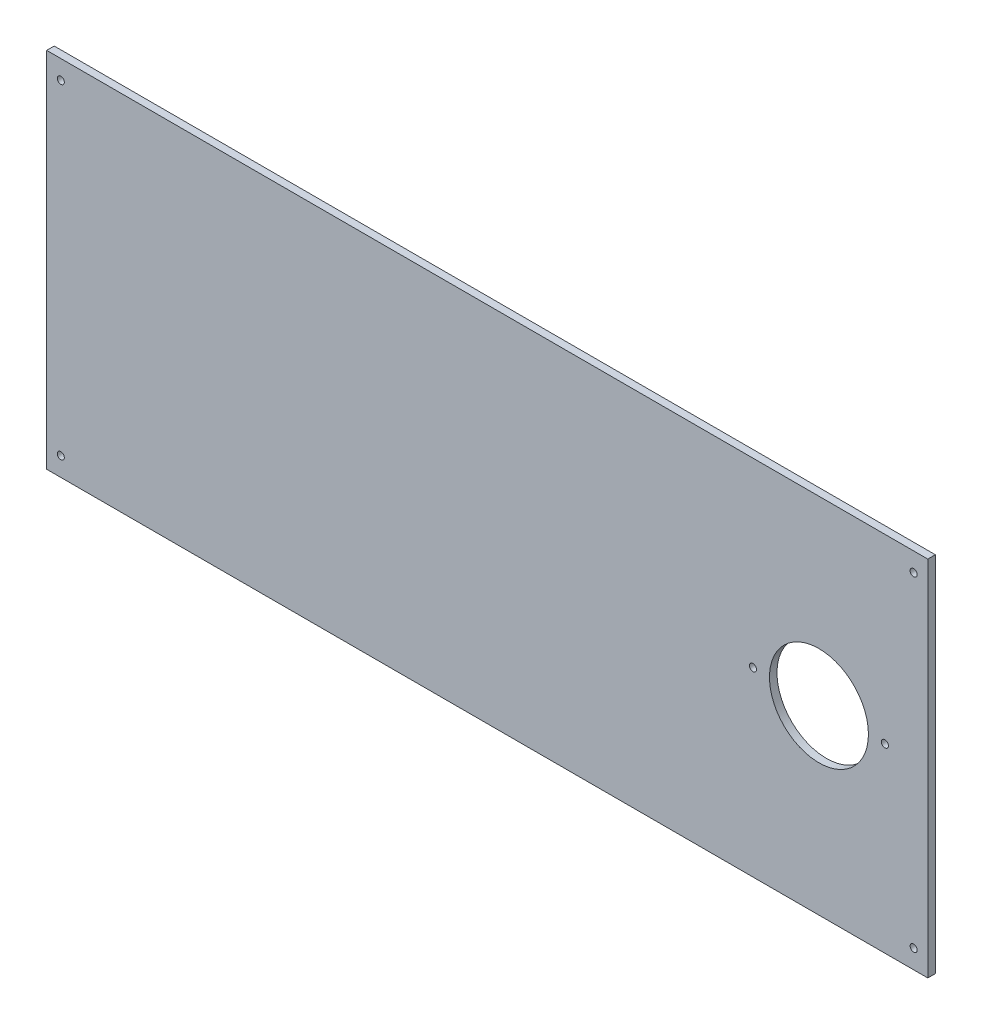
SolidWorks part; units mm, degrees
ref_plane "Спереди" through (0, 0, 0) normal (0, 0, 1) x (1, 0, 0)
ref_plane "Сверху" through (0, 0, 0) normal (0, 1, 0) x (1, 0, 0)
ref_plane "Справа" through (0, 0, 0) normal (1, 0, 0) x (0, 0, -1)
sketch "KeepOutLayer" plane through (0, 0, 0) normal (0, 0, 1) x (1, 0, 0)
  line L0 (0.0694, -77.068) -> (0.0694, -0.068)
  line L1 (0.0694, -0.068) -> (187.0694, -0.068)
  line L3 (187.0694, -77.068) -> (187.0694, -0.068)
  line L4 (0.0694, -77.068) -> (187.0694, -77.068)
  dimension "D1" = 187
  dimension "D2" = 77
  dimension "D3" = 0.068
  dimension "D4" = 0.0694
extrude "Бобышка-Вытянуть1" add sketch "KeepOutLayer" against normal blind 1.6
sketch "ViaHoleLayer" plane through (0, 0, 0) normal (0, 0, 1) x (1, 0, 0)
  line L0 (0.0694, -0.068) -> (0.0694, -77.068) construction
  line L1 (187.0694, -0.068) -> (0.0694, -0.068) construction
  line L2 (187.0694, -77.068) -> (187.0694, -0.068) construction
  line L3 (0.0694, -77.068) -> (187.0694, -77.068) construction
  circle A19 centre (3.0694, -73.068) radius 0.75
  circle A20 centre (3.0694, -4.068) radius 0.75
  circle A21 centre (184.0694, -73.068) radius 0.75
  circle A22 centre (184.0694, -4.068) radius 0.75
  circle A86 centre (149.9694, -38.568) radius 0.75
  circle A87 centre (177.9694, -38.568) radius 0.75
  circle A88 centre (163.9694, -38.568) radius 10.5
  dimension "D3" = 1.5
  dimension "D6" = 21
  dimension "D11" = 1.5
  dimension "D1" = 3
  dimension "D2" = 4
  dimension "D4" = 3
  dimension "D5" = 4
  dimension "D7" = 38.5
  dimension "D8" = 23.1
  dimension "D9" = 14
  dimension "D10" = 14
extrude "Вырез-Вытянуть1" cut sketch "ViaHoleLayer" against normal through all
sketch "TopOverlay" plane through (0, 0, 0) normal (0, 0, 1) x (1, 0, 0)
  line L0 (144.9694, -38.568) -> (145.2581, -35.2687)
  line L1 (167.2687, -19.8567) -> (170.4678, -20.7138)
  line L2 (173.4694, -22.1135) -> (176.1824, -24.0132)
  line L3 (167.2687, -57.2793) -> (170.4678, -56.4222)
  line L4 (173.4694, -55.0225) -> (176.1824, -53.1228)
  line L5 (157.471, -20.7138) -> (160.6701, -19.8567)
  line L6 (151.7564, -24.0132) -> (154.4694, -22.1135)
  line L7 (144.9694, -38.568) -> (145.2581, -41.8673)
  line L8 (151.7564, -53.1228) -> (154.4694, -55.0225)
  line L9 (157.471, -56.4222) -> (160.6701, -57.2793)
  line L10 (178.5242, -26.355) -> (180.4239, -29.068)
  line L11 (182.6807, -35.2687) -> (182.9694, -38.568)
  line L12 (176.1824, -53.1228) -> (178.5242, -50.781)
  line L13 (181.8236, -45.0664) -> (182.6807, -41.8673)
  line L14 (170.4678, -20.7138) -> (173.4694, -22.1135)
  line L15 (154.4694, -22.1135) -> (157.471, -20.7138)
  line L16 (147.5149, -29.068) -> (149.4146, -26.355)
  line L17 (145.2581, -41.8673) -> (146.1152, -45.0664)
  line L18 (149.4146, -50.781) -> (151.7564, -53.1228)
  line L19 (176.1824, -24.0132) -> (178.5242, -26.355)
  line L20 (181.8236, -32.0696) -> (182.6807, -35.2687)
  line L21 (180.4239, -29.068) -> (181.8236, -32.0696)
  line L22 (182.6807, -41.8673) -> (182.9694, -38.568)
  line L23 (178.5242, -50.781) -> (180.4239, -48.068)
  line L24 (180.4239, -48.068) -> (181.8236, -45.0664)
  line L25 (170.4678, -56.4222) -> (173.4694, -55.0225)
  line L26 (163.9694, -19.568) -> (167.2687, -19.8567)
  line L27 (160.6701, -19.8567) -> (163.9694, -19.568)
  line L28 (160.6701, -57.2793) -> (163.9694, -57.568)
  line L29 (163.9694, -57.568) -> (167.2687, -57.2793)
  line L30 (154.4694, -55.0225) -> (157.471, -56.4222)
  line L31 (149.4146, -26.355) -> (151.7564, -24.0132)
  line L32 (146.1152, -32.0696) -> (147.5149, -29.068)
  line L33 (145.2581, -35.2687) -> (146.1152, -32.0696)
  line L34 (146.1152, -45.0664) -> (147.5149, -48.068)
  line L35 (147.5149, -48.068) -> (149.4146, -50.781)
  line L36 (152.5964, -11.5741) -> (152.5964, -13.0619)
  line L37 (152.5964, -13.0619) -> (152.6956, -13.3594)
  line L38 (152.6956, -13.3594) -> (152.894, -13.5578)
  line L39 (152.894, -13.5578) -> (153.1915, -13.657)
  line L40 (153.1915, -13.657) -> (153.3899, -13.657)
  line L41 (153.3899, -13.657) -> (153.6874, -13.5578)
  line L42 (153.6874, -13.5578) -> (153.8858, -13.3594)
  line L43 (153.8858, -13.3594) -> (153.985, -13.0619)
  line L44 (153.985, -13.0619) -> (153.985, -11.5741)
  line L45 (156.1472, -13.657) -> (155.3537, -11.5741)
  line L46 (155.3537, -11.5741) -> (154.5602, -13.657)
  line L47 (154.8578, -12.9627) -> (155.8496, -12.9627)
  line L48 (156.8316, -11.5741) -> (157.9226, -11.5741)
  line L49 (157.9226, -11.5741) -> (157.3275, -12.3676)
  line L50 (157.3275, -12.3676) -> (157.625, -12.3676)
  line L51 (157.625, -12.3676) -> (157.8234, -12.4668)
  line L52 (157.8234, -12.4668) -> (157.9226, -12.566)
  line L53 (157.9226, -12.566) -> (158.0218, -12.8635)
  line L54 (158.0218, -12.8635) -> (158.0218, -13.0619)
  line L55 (158.0218, -13.0619) -> (157.9226, -13.3594)
  line L56 (157.9226, -13.3594) -> (157.7242, -13.5578)
  line L57 (157.7242, -13.5578) -> (157.4267, -13.657)
  line L58 (157.4267, -13.657) -> (157.1291, -13.657)
  line L59 (157.1291, -13.657) -> (156.8316, -13.5578)
  line L60 (156.8316, -13.5578) -> (156.7324, -13.4586)
  line L61 (156.7324, -13.4586) -> (156.6332, -13.2603)
  line L62 (158.4879, -11.5741) -> (158.4879, -13.657)
  line L63 (158.4879, -11.5741) -> (159.3806, -11.5741)
  line L64 (159.3806, -11.5741) -> (159.6781, -11.6733)
  line L65 (159.6781, -11.6733) -> (159.7773, -11.7725)
  line L66 (159.7773, -11.7725) -> (159.8765, -11.9709)
  line L67 (159.8765, -11.9709) -> (159.8765, -12.1692)
  line L68 (159.8765, -12.1692) -> (159.7773, -12.3676)
  line L69 (159.7773, -12.3676) -> (159.6781, -12.4668)
  line L70 (159.6781, -12.4668) -> (159.3806, -12.566)
  line L71 (159.3806, -12.566) -> (158.4879, -12.566)
  line L72 (159.1822, -12.566) -> (159.8765, -13.657)
  line L73 (161.6321, -11.5741) -> (160.3427, -11.5741)
  line L74 (160.3427, -11.5741) -> (160.3427, -13.657)
  line L75 (160.3427, -13.657) -> (161.6321, -13.657)
  line L76 (160.3427, -12.566) -> (161.1362, -12.566)
  line L77 (162.5743, -11.5741) -> (162.376, -11.6733)
  line L78 (162.376, -11.6733) -> (162.1776, -11.8717)
  line L79 (162.1776, -11.8717) -> (162.0784, -12.0701)
  line L80 (162.0784, -12.0701) -> (161.9792, -12.3676)
  line L81 (161.9792, -12.3676) -> (161.9792, -12.8635)
  line L82 (161.9792, -12.8635) -> (162.0784, -13.1611)
  line L83 (162.0784, -13.1611) -> (162.1776, -13.3594)
  line L84 (162.1776, -13.3594) -> (162.376, -13.5578)
  line L85 (162.376, -13.5578) -> (162.5743, -13.657)
  line L86 (162.5743, -13.657) -> (162.9711, -13.657)
  line L87 (162.9711, -13.657) -> (163.1694, -13.5578)
  line L88 (163.1694, -13.5578) -> (163.3678, -13.3594)
  line L89 (163.3678, -13.3594) -> (163.467, -13.1611)
  line L90 (163.467, -13.1611) -> (163.5662, -12.8635)
  line L91 (163.5662, -12.8635) -> (163.5662, -12.3676)
  line L92 (163.5662, -12.3676) -> (163.467, -12.0701)
  line L93 (163.467, -12.0701) -> (163.3678, -11.8717)
  line L94 (163.3678, -11.8717) -> (163.1694, -11.6733)
  line L95 (163.1694, -11.6733) -> (162.9711, -11.5741)
  line L96 (162.9711, -11.5741) -> (162.5743, -11.5741)
  line L97 (166.383, -11.5741) -> (166.383, -13.657)
  line L98 (165.6887, -11.5741) -> (167.0773, -11.5741)
  line L99 (167.3252, -12.2684) -> (167.3252, -13.657)
  line L100 (167.3252, -12.8635) -> (167.4244, -12.566)
  line L101 (167.4244, -12.566) -> (167.6228, -12.3676)
  line L102 (167.6228, -12.3676) -> (167.8212, -12.2684)
  line L103 (167.8212, -12.2684) -> (168.1187, -12.2684)
  line L104 (169.4974, -12.2684) -> (169.4974, -13.657)
  line L105 (169.4974, -12.566) -> (169.299, -12.3676)
  line L106 (169.299, -12.3676) -> (169.1006, -12.2684)
  line L107 (169.1006, -12.2684) -> (168.8031, -12.2684)
  line L108 (168.8031, -12.2684) -> (168.6047, -12.3676)
  line L109 (168.6047, -12.3676) -> (168.4063, -12.566)
  line L110 (168.4063, -12.566) -> (168.3072, -12.8635)
  line L111 (168.3072, -12.8635) -> (168.3072, -13.0619)
  line L112 (168.3072, -13.0619) -> (168.4063, -13.3594)
  line L113 (168.4063, -13.3594) -> (168.6047, -13.5578)
  line L114 (168.6047, -13.5578) -> (168.8031, -13.657)
  line L115 (168.8031, -13.657) -> (169.1006, -13.657)
  line L116 (169.1006, -13.657) -> (169.299, -13.5578)
  line L117 (169.299, -13.5578) -> (169.4974, -13.3594)
  line L118 (170.0528, -12.2684) -> (170.0528, -13.657)
  line L119 (170.0528, -12.6652) -> (170.3504, -12.3676)
  line L120 (170.3504, -12.3676) -> (170.5487, -12.2684)
  line L121 (170.5487, -12.2684) -> (170.8463, -12.2684)
  line L122 (170.8463, -12.2684) -> (171.0446, -12.3676)
  line L123 (171.0446, -12.3676) -> (171.1438, -12.6652)
  line L124 (171.1438, -12.6652) -> (171.1438, -13.657)
  line L125 (172.7804, -12.566) -> (172.6812, -12.3676)
  line L126 (172.6812, -12.3676) -> (172.3836, -12.2684)
  line L127 (172.3836, -12.2684) -> (172.0861, -12.2684)
  line L128 (172.0861, -12.2684) -> (171.7885, -12.3676)
  line L129 (171.7885, -12.3676) -> (171.6893, -12.566)
  line L130 (171.6893, -12.566) -> (171.7885, -12.7643)
  line L131 (171.7885, -12.7643) -> (171.9869, -12.8635)
  line L132 (171.9869, -12.8635) -> (172.4828, -12.9627)
  line L133 (172.4828, -12.9627) -> (172.6812, -13.0619)
  line L134 (172.6812, -13.0619) -> (172.7804, -13.2603)
  line L135 (172.7804, -13.2603) -> (172.7804, -13.3594)
  line L136 (172.7804, -13.3594) -> (172.6812, -13.5578)
  line L137 (172.6812, -13.5578) -> (172.3836, -13.657)
  line L138 (172.3836, -13.657) -> (172.0861, -13.657)
  line L139 (172.0861, -13.657) -> (171.7885, -13.5578)
  line L140 (171.7885, -13.5578) -> (171.6893, -13.3594)
  line L141 (174.407, -12.566) -> (174.2086, -12.3676)
  line L142 (174.2086, -12.3676) -> (174.0103, -12.2684)
  line L143 (174.0103, -12.2684) -> (173.7127, -12.2684)
  line L144 (173.7127, -12.2684) -> (173.5143, -12.3676)
  line L145 (173.5143, -12.3676) -> (173.316, -12.566)
  line L146 (173.316, -12.566) -> (173.2168, -12.8635)
  line L147 (173.2168, -12.8635) -> (173.2168, -13.0619)
  line L148 (173.2168, -13.0619) -> (173.316, -13.3594)
  line L149 (173.316, -13.3594) -> (173.5143, -13.5578)
  line L150 (173.5143, -13.5578) -> (173.7127, -13.657)
  line L151 (173.7127, -13.657) -> (174.0103, -13.657)
  line L152 (174.0103, -13.657) -> (174.2086, -13.5578)
  line L153 (174.2086, -13.5578) -> (174.407, -13.3594)
  line L154 (174.8533, -12.8635) -> (176.0435, -12.8635)
  line L155 (176.0435, -12.8635) -> (176.0435, -12.6652)
  line L156 (176.0435, -12.6652) -> (175.9443, -12.4668)
  line L157 (175.9443, -12.4668) -> (175.8452, -12.3676)
  line L158 (175.8452, -12.3676) -> (175.6468, -12.2684)
  line L159 (175.6468, -12.2684) -> (175.3492, -12.2684)
  line L160 (175.3492, -12.2684) -> (175.1509, -12.3676)
  line L161 (175.1509, -12.3676) -> (174.9525, -12.566)
  line L162 (174.9525, -12.566) -> (174.8533, -12.8635)
  line L163 (174.8533, -12.8635) -> (174.8533, -13.0619)
  line L164 (174.8533, -13.0619) -> (174.9525, -13.3594)
  line L165 (174.9525, -13.3594) -> (175.1509, -13.5578)
  line L166 (175.1509, -13.5578) -> (175.3492, -13.657)
  line L167 (175.3492, -13.657) -> (175.6468, -13.657)
  line L168 (175.6468, -13.657) -> (175.8452, -13.5578)
  line L169 (175.8452, -13.5578) -> (176.0435, -13.3594)
  line L170 (176.6882, -11.5741) -> (176.7874, -11.6733)
  line L171 (176.7874, -11.6733) -> (176.8866, -11.5741)
  line L172 (176.8866, -11.5741) -> (176.7874, -11.475)
  line L173 (176.7874, -11.475) -> (176.6882, -11.5741)
  line L174 (176.7874, -12.2684) -> (176.7874, -13.657)
  line L175 (177.2536, -12.2684) -> (177.8487, -13.657)
  line L176 (178.4438, -12.2684) -> (177.8487, -13.657)
  line L177 (178.781, -12.8635) -> (179.9712, -12.8635)
  line L178 (179.9712, -12.8635) -> (179.9712, -12.6652)
  line L179 (179.9712, -12.6652) -> (179.872, -12.4668)
  line L180 (179.872, -12.4668) -> (179.7728, -12.3676)
  line L181 (179.7728, -12.3676) -> (179.5745, -12.2684)
  line L182 (179.5745, -12.2684) -> (179.2769, -12.2684)
  line L183 (179.2769, -12.2684) -> (179.0786, -12.3676)
  line L184 (179.0786, -12.3676) -> (178.8802, -12.566)
  line L185 (178.8802, -12.566) -> (178.781, -12.8635)
  line L186 (178.781, -12.8635) -> (178.781, -13.0619)
  line L187 (178.781, -13.0619) -> (178.8802, -13.3594)
  line L188 (178.8802, -13.3594) -> (179.0786, -13.5578)
  line L189 (179.0786, -13.5578) -> (179.2769, -13.657)
  line L190 (179.2769, -13.657) -> (179.5745, -13.657)
  line L191 (179.5745, -13.657) -> (179.7728, -13.5578)
  line L192 (179.7728, -13.5578) -> (179.9712, -13.3594)
  line L193 (180.4175, -12.2684) -> (180.4175, -13.657)
  line L194 (180.4175, -12.8635) -> (180.5167, -12.566)
  line L195 (180.5167, -12.566) -> (180.7151, -12.3676)
  line L196 (180.7151, -12.3676) -> (180.9135, -12.2684)
  line L197 (180.9135, -12.2684) -> (181.211, -12.2684)
  line L198 (160.7345, -73.8642) -> (160.7345, -75.114)
  line L199 (160.7345, -73.8642) -> (161.5081, -73.8642)
  line L200 (160.7345, -74.4593) -> (161.2106, -74.4593)
  line L201 (161.651, -73.8642) -> (161.651, -75.114)
  line L202 (161.651, -73.8642) -> (162.1866, -73.8642)
  line L203 (162.1866, -73.8642) -> (162.3651, -73.9237)
  line L204 (162.3651, -73.9237) -> (162.4246, -73.9832)
  line L205 (162.4246, -73.9832) -> (162.4841, -74.1023)
  line L206 (162.4841, -74.1023) -> (162.4841, -74.2213)
  line L207 (162.4841, -74.2213) -> (162.4246, -74.3403)
  line L208 (162.4246, -74.3403) -> (162.3651, -74.3998)
  line L209 (162.3651, -74.3998) -> (162.1866, -74.4593)
  line L210 (162.1866, -74.4593) -> (161.651, -74.4593)
  line L211 (162.0675, -74.4593) -> (162.4841, -75.114)
  line L212 (163.1209, -73.8642) -> (163.0019, -73.9237)
  line L213 (163.0019, -73.9237) -> (162.8828, -74.0428)
  line L214 (162.8828, -74.0428) -> (162.8233, -74.1618)
  line L215 (162.8233, -74.1618) -> (162.7638, -74.3403)
  line L216 (162.7638, -74.3403) -> (162.7638, -74.6379)
  line L217 (162.7638, -74.6379) -> (162.8233, -74.8164)
  line L218 (162.8233, -74.8164) -> (162.8828, -74.9354)
  line L219 (162.8828, -74.9354) -> (163.0019, -75.0544)
  line L220 (163.0019, -75.0544) -> (163.1209, -75.114)
  line L221 (163.1209, -75.114) -> (163.3589, -75.114)
  line L222 (163.3589, -75.114) -> (163.478, -75.0544)
  line L223 (163.478, -75.0544) -> (163.597, -74.9354)
  line L224 (163.597, -74.9354) -> (163.6565, -74.8164)
  line L225 (163.6565, -74.8164) -> (163.716, -74.6379)
  line L226 (163.716, -74.6379) -> (163.716, -74.3403)
  line L227 (163.716, -74.3403) -> (163.6565, -74.1618)
  line L228 (163.6565, -74.1618) -> (163.597, -74.0428)
  line L229 (163.597, -74.0428) -> (163.478, -73.9237)
  line L230 (163.478, -73.9237) -> (163.3589, -73.8642)
  line L231 (163.3589, -73.8642) -> (163.1209, -73.8642)
  line L232 (164.0076, -73.8642) -> (164.0076, -75.114)
  line L233 (164.0076, -73.8642) -> (164.8408, -75.114)
  line L234 (164.8408, -73.8642) -> (164.8408, -75.114)
  line L235 (165.6025, -73.8642) -> (165.6025, -75.114)
  line L236 (165.1859, -73.8642) -> (166.0191, -73.8642)
  line L237 (166.1679, -74.5784) -> (167.2391, -74.5784)
  line L238 (167.608, -73.8642) -> (167.608, -74.7569)
  line L239 (167.608, -74.7569) -> (167.6675, -74.9354)
  line L240 (167.6675, -74.9354) -> (167.7866, -75.0544)
  line L241 (167.7866, -75.0544) -> (167.9651, -75.114)
  line L242 (167.9651, -75.114) -> (168.0841, -75.114)
  line L243 (168.0841, -75.114) -> (168.2627, -75.0544)
  line L244 (168.2627, -75.0544) -> (168.3817, -74.9354)
  line L245 (168.3817, -74.9354) -> (168.4412, -74.7569)
  line L246 (168.4412, -74.7569) -> (168.4412, -73.8642)
  line L247 (168.7863, -73.8642) -> (168.7863, -75.114)
  line L248 (168.7863, -73.8642) -> (169.6195, -75.114)
  line L249 (169.6195, -73.8642) -> (169.6195, -75.114)
  line L250 (169.9647, -73.8642) -> (169.9647, -75.114)
  line L251 (170.6431, -73.8642) -> (170.6431, -75.114)
  line L252 (170.2265, -73.8642) -> (171.0597, -73.8642)
  line L253 (172.1904, -74.2808) -> (172.1904, -75.114)
  line L254 (172.1904, -74.6379) -> (172.2499, -74.4593)
  line L255 (172.2499, -74.4593) -> (172.3689, -74.3403)
  line L256 (172.3689, -74.3403) -> (172.4879, -74.2808)
  line L257 (172.4879, -74.2808) -> (172.6665, -74.2808)
  line L258 (172.7795, -74.6379) -> (173.4937, -74.6379)
  line L259 (173.4937, -74.6379) -> (173.4937, -74.5188)
  line L260 (173.4937, -74.5188) -> (173.4342, -74.3998)
  line L261 (173.4342, -74.3998) -> (173.3747, -74.3403)
  line L262 (173.3747, -74.3403) -> (173.2556, -74.2808)
  line L263 (173.2556, -74.2808) -> (173.0771, -74.2808)
  line L264 (173.0771, -74.2808) -> (172.9581, -74.3403)
  line L265 (172.9581, -74.3403) -> (172.8391, -74.4593)
  line L266 (172.8391, -74.4593) -> (172.7795, -74.6379)
  line L267 (172.7795, -74.6379) -> (172.7795, -74.7569)
  line L268 (172.7795, -74.7569) -> (172.8391, -74.9354)
  line L269 (172.8391, -74.9354) -> (172.9581, -75.0544)
  line L270 (172.9581, -75.0544) -> (173.0771, -75.114)
  line L271 (173.0771, -75.114) -> (173.2556, -75.114)
  line L272 (173.2556, -75.114) -> (173.3747, -75.0544)
  line L273 (173.3747, -75.0544) -> (173.4937, -74.9354)
  line L274 (173.7615, -74.2808) -> (174.1185, -75.114)
  line L275 (174.4756, -74.2808) -> (174.1185, -75.114)
  line L276 (175.3921, -74.0428) -> (175.3326, -73.9237)
  line L277 (175.3326, -73.9237) -> (175.154, -73.8642)
  line L278 (175.154, -73.8642) -> (175.035, -73.8642)
  line L279 (175.035, -73.8642) -> (174.8565, -73.9237)
  line L280 (174.8565, -73.9237) -> (174.7375, -74.1023)
  line L281 (174.7375, -74.1023) -> (174.6779, -74.3998)
  line L282 (174.6779, -74.3998) -> (174.6779, -74.6974)
  line L283 (174.6779, -74.6974) -> (174.7375, -74.9354)
  line L284 (174.7375, -74.9354) -> (174.8565, -75.0544)
  line L285 (174.8565, -75.0544) -> (175.035, -75.114)
  line L286 (175.035, -75.114) -> (175.0945, -75.114)
  line L287 (175.0945, -75.114) -> (175.2731, -75.0544)
  line L288 (175.2731, -75.0544) -> (175.3921, -74.9354)
  line L289 (175.3921, -74.9354) -> (175.4516, -74.7569)
  line L290 (175.4516, -74.7569) -> (175.4516, -74.6974)
  line L291 (175.4516, -74.6974) -> (175.3921, -74.5188)
  line L292 (175.3921, -74.5188) -> (175.2731, -74.3998)
  line L293 (175.2731, -74.3998) -> (175.0945, -74.3403)
  line L294 (175.0945, -74.3403) -> (175.035, -74.3403)
  line L295 (175.035, -74.3403) -> (174.8565, -74.3998)
  line L296 (174.8565, -74.3998) -> (174.7375, -74.5188)
  line L297 (174.7375, -74.5188) -> (174.6779, -74.6974)
  line L298 (18.2304, -10.609) -> (18.2304, -6.5609) construction
  line L299 (103.8841, -2.9565) -> (97.1392, -2.9565) construction
  line L300 (94.4282, -2.9565) -> (83.2818, -2.9565) construction
  line L301 (22.8573, -3.3095) -> (21.179, -3.3095) construction
  line L302 (44.2808, -3.3095) -> (39.2143, -3.3095) construction
  line L303 (91.1079, -69.5367) -> (91.1079, -66.8451) construction
  line L304 (77.7079, -69.5126) -> (77.7079, -66.821) construction
  line L305 (46.9079, -70.9597) -> (46.9079, -68.9331) construction
  line L306 (39.8079, -46.5092) -> (39.8079, -44.4826) construction
  line L307 (15.0554, -52.773) -> (15.0554, -50.7464) construction
  line L308 (22.8079, -70.9833) -> (22.8079, -68.9567) construction
  line L309 (117.9079, -69.4879) -> (117.9079, -66.7963) construction
  line L310 (104.5079, -69.5126) -> (104.5079, -66.821) construction
  line L311 (64.5079, -69.5126) -> (64.5079, -66.821) construction
  line L312 (51.1079, -69.2942) -> (51.1079, -66.9509) construction
  line L313 (34.9079, -71.2626) -> (34.9079, -68.761) construction
  line L314 (27.9079, -46.0339) -> (27.9079, -44.0073) construction
  line L315 (11.0079, -70.9839) -> (11.0079, -68.9573) construction
  circle A0 centre (144.9694, -38.568) radius 0.075
  circle A1 centre (145.2581, -35.2687) radius 0.075
  circle A2 centre (167.2687, -19.8567) radius 0.075
  circle A3 centre (170.4678, -20.7138) radius 0.075
  circle A4 centre (173.4694, -22.1135) radius 0.075
  circle A5 centre (176.1824, -24.0132) radius 0.075
  circle A6 centre (167.2687, -57.2793) radius 0.075
  circle A7 centre (170.4678, -56.4222) radius 0.075
  circle A8 centre (173.4694, -55.0225) radius 0.075
  circle A9 centre (176.1824, -53.1228) radius 0.075
  circle A10 centre (157.471, -20.7138) radius 0.075
  circle A11 centre (160.6701, -19.8567) radius 0.075
  circle A12 centre (151.7564, -24.0132) radius 0.075
  circle A13 centre (154.4694, -22.1135) radius 0.075
  circle A14 centre (144.9694, -38.568) radius 0.075
  circle A15 centre (145.2581, -41.8673) radius 0.075
  circle A16 centre (151.7564, -53.1228) radius 0.075
  circle A17 centre (154.4694, -55.0225) radius 0.075
  circle A18 centre (157.471, -56.4222) radius 0.075
  circle A19 centre (160.6701, -57.2793) radius 0.075
  circle A20 centre (178.5242, -26.355) radius 0.075
  circle A21 centre (180.4239, -29.068) radius 0.075
  circle A22 centre (182.6807, -35.2687) radius 0.075
  circle A23 centre (182.9694, -38.568) radius 0.075
  circle A24 centre (176.1824, -53.1228) radius 0.075
  circle A25 centre (178.5242, -50.781) radius 0.075
  circle A26 centre (181.8236, -45.0664) radius 0.075
  circle A27 centre (182.6807, -41.8673) radius 0.075
  circle A28 centre (170.4678, -20.7138) radius 0.075
  circle A29 centre (173.4694, -22.1135) radius 0.075
  circle A30 centre (154.4694, -22.1135) radius 0.075
  circle A31 centre (157.471, -20.7138) radius 0.075
  circle A32 centre (147.5149, -29.068) radius 0.075
  circle A33 centre (149.4146, -26.355) radius 0.075
  circle A34 centre (145.2581, -41.8673) radius 0.075
  circle A35 centre (146.1152, -45.0664) radius 0.075
  circle A36 centre (149.4146, -50.781) radius 0.075
  circle A37 centre (151.7564, -53.1228) radius 0.075
  circle A38 centre (176.1824, -24.0132) radius 0.075
  circle A39 centre (178.5242, -26.355) radius 0.075
  circle A40 centre (181.8236, -32.0696) radius 0.075
  circle A41 centre (182.6807, -35.2687) radius 0.075
  circle A42 centre (180.4239, -29.068) radius 0.075
  circle A43 centre (181.8236, -32.0696) radius 0.075
  circle A44 centre (182.6807, -41.8673) radius 0.075
  circle A45 centre (182.9694, -38.568) radius 0.075
  circle A46 centre (178.5242, -50.781) radius 0.075
  circle A47 centre (180.4239, -48.068) radius 0.075
  circle A48 centre (180.4239, -48.068) radius 0.075
  circle A49 centre (181.8236, -45.0664) radius 0.075
  circle A50 centre (170.4678, -56.4222) radius 0.075
  circle A51 centre (173.4694, -55.0225) radius 0.075
  circle A52 centre (163.9694, -19.568) radius 0.075
  circle A53 centre (167.2687, -19.8567) radius 0.075
  circle A54 centre (160.6701, -19.8567) radius 0.075
  circle A55 centre (163.9694, -19.568) radius 0.075
  circle A56 centre (160.6701, -57.2793) radius 0.075
  circle A57 centre (163.9694, -57.568) radius 0.075
  circle A58 centre (163.9694, -57.568) radius 0.075
  circle A59 centre (167.2687, -57.2793) radius 0.075
  circle A60 centre (154.4694, -55.0225) radius 0.075
  circle A61 centre (157.471, -56.4222) radius 0.075
  circle A62 centre (149.4146, -26.355) radius 0.075
  circle A63 centre (151.7564, -24.0132) radius 0.075
  circle A64 centre (146.1152, -32.0696) radius 0.075
  circle A65 centre (147.5149, -29.068) radius 0.075
  circle A66 centre (145.2581, -35.2687) radius 0.075
  circle A67 centre (146.1152, -32.0696) radius 0.075
  circle A68 centre (146.1152, -45.0664) radius 0.075
  circle A69 centre (147.5149, -48.068) radius 0.075
  circle A70 centre (147.5149, -48.068) radius 0.075
  circle A71 centre (149.4146, -50.781) radius 0.075
  text T0 "S15" font "SWTXT" height 1.524
  text T1 "PWR" font "SWTXT" height 1.524
  text T2 "S4" font "SWTXT" height 1.0133
  text T3 "MODE+" font "SWTXT" height 1.9304
  text T4 "RF-UNIT" font "SWTXT" height 1.0133
  text T5 "R1" font "SWTXT" height 1.0133
  text T6 "AF GAIN" font "SWTXT" height 1.9304
  text T7 "S8" font "SWTXT" height 1.0133
  text T8 "A/B" font "SWTXT" height 1.9304
  text T9 "S5" font "SWTXT" height 1.0133
  text T10 "FAST" font "SWTXT" height 1.9304
  text T11 "ENC2" font "SWTXT" height 1.0133
  text T12 "S1" font "SWTXT" height 1.0133
  text T13 "BAND-" font "SWTXT" height 1.9304
  text T14 "C1" font "SWTXT" height 1.0133
  text T15 "S10" font "SWTXT" height 1.0133
  text T16 "DNR" font "SWTXT" height 1.9304
  text T17 "R18" font "SWTXT" height 1.0133
  text T18 "MOTHERBOARD" font "SWTXT" height 1.0133
  text T19 "R2" font "SWTXT" height 1.0133
  text T20 "SHIFT" font "SWTXT" height 1.9304
  text T21 "S7" font "SWTXT" height 1.0133
  text T22 "TUNE" font "SWTXT" height 1.9304
  text T23 "S6" font "SWTXT" height 1.0133
  text T24 "PRE/ATT" font "SWTXT" height 1.9304
  text T25 "IN" font "SWTXT" height 1.0133
  text T26 "ACCUM" font "SWTXT" height 1.0133
  text T27 "S14" font "SWTXT" height 1.0133
  text T28 "MENU" font "SWTXT" height 1.9304
  text T29 "S13" font "SWTXT" height 1.0133
  text T30 "CLAR" font "SWTXT" height 1.9304
  text T31 "S12" font "SWTXT" height 1.0133
  text T32 "NOTCH" font "SWTXT" height 1.9304
  text T33 "S11" font "SWTXT" height 1.0133
  text T34 "A=B" font "SWTXT" height 1.9304
  text T35 "R14" font "SWTXT" height 1.0133
  text T36 "R13" font "SWTXT" height 1.0133
  text T37 "S9" font "SWTXT" height 1.0133
  text T38 "AGC" font "SWTXT" height 1.9304
  text T39 "S3" font "SWTXT" height 1.0133
  text T40 "MODE-" font "SWTXT" height 1.9304
  text T41 "S2" font "SWTXT" height 1.0133
  text T42 "BAND+" font "SWTXT" height 1.9304
  text T43 "C2" font "SWTXT" height 1.0133
  text T44 "R9" font "SWTXT" height 1.0133
  text T45 "R17" font "SWTXT" height 1.0133
  text T46 "R6" font "SWTXT" height 1.0133
  text T47 "R4" font "SWTXT" height 1.0133
  text T48 "R8" font "SWTXT" height 1.0133
  text T49 "R16" font "SWTXT" height 1.0133
  text T50 "R15" font "SWTXT" height 1.0133
  text T51 "R12" font "SWTXT" height 1.0133
  text T52 "R11" font "SWTXT" height 1.0133
  text T53 "R19" font "SWTXT" height 1.0133
  text T54 "R3" font "SWTXT" height 1.0133
  text T55 "R10" font "SWTXT" height 1.0133
  text T56 "R5" font "SWTXT" height 1.0133
  text T57 "R7" font "SWTXT" height 1.0133
sketch "0" plane through (0, 0, 0) normal (0, 0, 1) x (1, 0, 0)
  line L0 (15.6902, -7.1802) -> (15.6902, -5.9098)
  line L1 (8.0706, -7.1802) -> (8.0706, -5.9098)
  line L2 (9.9759, -9.7195) -> (13.7849, -9.7195)
  line L3 (9.9759, -3.3699) -> (13.7849, -3.3699)
  line L4 (42.8149, -46.8929) -> (46.6239, -46.8929)
  line L5 (42.8149, -53.2425) -> (46.6239, -53.2425)
  line L6 (40.9096, -50.7032) -> (40.9096, -49.4328)
  line L7 (48.5292, -50.7032) -> (48.5292, -49.4328)
  line L8 (80.7904, -57.47) -> (80.7904, -55.438)
  line L9 (74.7904, -57.47) -> (74.7904, -55.438)
  line L10 (52.7904, -57.668) -> (143.7904, -57.368)
  line L11 (143.7904, -57.368) -> (143.7904, -3.368)
  line L12 (52.7904, -3.368) -> (143.7904, -3.368)
  line L13 (52.7904, -57.597) -> (52.7904, -3.368)
  line L14 (138.622, -7.43) -> (143.7089, -7.43)
  line L15 (143.7089, -53.152) -> (143.7089, -7.43)
  line L16 (138.622, -53.152) -> (143.7089, -53.152)
  line L17 (138.622, -53.152) -> (138.622, -7.43)
  line L18 (58.8704, -4.368) -> (136.7904, -4.368)
  line L19 (58.8704, -4.368) -> (58.8704, -55.2681)
  line L20 (58.8704, -55.2681) -> (136.7904, -55.368)
  line L21 (136.7904, -55.368) -> (136.7904, -4.368)
  line L22 (93.5767, -29.3997) -> (93.5767, -31.0661)
  line L23 (93.5767, -31.0661) -> (94.5289, -31.0661)
  line L24 (95.9016, -29.7965) -> (95.8223, -29.6378)
  line L25 (95.8223, -29.6378) -> (95.6636, -29.4791)
  line L26 (95.6636, -29.4791) -> (95.5049, -29.3997)
  line L27 (95.5049, -29.3997) -> (95.1875, -29.3997)
  line L28 (95.1875, -29.3997) -> (95.0288, -29.4791)
  line L29 (95.0288, -29.4791) -> (94.8701, -29.6378)
  line L30 (94.8701, -29.6378) -> (94.7907, -29.7965)
  line L31 (94.7907, -29.7965) -> (94.7114, -30.0345)
  line L32 (94.7114, -30.0345) -> (94.7114, -30.4313)
  line L33 (94.7114, -30.4313) -> (94.7907, -30.6693)
  line L34 (94.7907, -30.6693) -> (94.8701, -30.828)
  line L35 (94.8701, -30.828) -> (95.0288, -30.9867)
  line L36 (95.0288, -30.9867) -> (95.1875, -31.0661)
  line L37 (95.1875, -31.0661) -> (95.5049, -31.0661)
  line L38 (95.5049, -31.0661) -> (95.6636, -30.9867)
  line L39 (95.6636, -30.9867) -> (95.8223, -30.828)
  line L40 (95.8223, -30.828) -> (95.9016, -30.6693)
  line L41 (96.3698, -29.3997) -> (96.3698, -31.0661)
  line L42 (96.3698, -29.3997) -> (96.9252, -29.3997)
  line L43 (96.9252, -29.3997) -> (97.1633, -29.4791)
  line L44 (97.1633, -29.4791) -> (97.322, -29.6378)
  line L45 (97.322, -29.6378) -> (97.4013, -29.7965)
  line L46 (97.4013, -29.7965) -> (97.4807, -30.0345)
  line L47 (97.4807, -30.0345) -> (97.4807, -30.4313)
  line L48 (97.4807, -30.4313) -> (97.4013, -30.6693)
  line L49 (97.4013, -30.6693) -> (97.322, -30.828)
  line L50 (97.322, -30.828) -> (97.1633, -30.9867)
  line L51 (97.1633, -30.9867) -> (96.9252, -31.0661)
  line L52 (96.9252, -31.0661) -> (96.3698, -31.0661)
  line L53 (97.8536, -30.3519) -> (99.2819, -30.3519)
  line L54 (99.7738, -29.3997) -> (99.7738, -31.0661)
  line L55 (99.7738, -29.3997) -> (100.4086, -31.0661)
  line L56 (101.0434, -29.3997) -> (100.4086, -31.0661)
  line L57 (101.0434, -29.3997) -> (101.0434, -31.0661)
  line L58 (101.9956, -29.3997) -> (101.8369, -29.4791)
  line L59 (101.8369, -29.4791) -> (101.6782, -29.6378)
  line L60 (101.6782, -29.6378) -> (101.5989, -29.7965)
  line L61 (101.5989, -29.7965) -> (101.5195, -30.0345)
  line L62 (101.5195, -30.0345) -> (101.5195, -30.4313)
  line L63 (101.5195, -30.4313) -> (101.5989, -30.6693)
  line L64 (101.5989, -30.6693) -> (101.6782, -30.828)
  line L65 (101.6782, -30.828) -> (101.8369, -30.9867)
  line L66 (101.8369, -30.9867) -> (101.9956, -31.0661)
  line L67 (101.9956, -31.0661) -> (102.313, -31.0661)
  line L68 (102.313, -31.0661) -> (102.4717, -30.9867)
  line L69 (102.4717, -30.9867) -> (102.6304, -30.828)
  line L70 (102.6304, -30.828) -> (102.7098, -30.6693)
  line L71 (102.7098, -30.6693) -> (102.7891, -30.4313)
  line L72 (102.7891, -30.4313) -> (102.7891, -30.0345)
  line L73 (102.7891, -30.0345) -> (102.7098, -29.7965)
  line L74 (102.7098, -29.7965) -> (102.6304, -29.6378)
  line L75 (102.6304, -29.6378) -> (102.4717, -29.4791)
  line L76 (102.4717, -29.4791) -> (102.313, -29.3997)
  line L77 (102.313, -29.3997) -> (101.9956, -29.3997)
  line L78 (103.1779, -29.3997) -> (103.1779, -31.0661)
  line L79 (103.1779, -29.3997) -> (103.7334, -29.3997)
  line L80 (103.7334, -29.3997) -> (103.9714, -29.4791)
  line L81 (103.9714, -29.4791) -> (104.1301, -29.6378)
  line L82 (104.1301, -29.6378) -> (104.2095, -29.7965)
  line L83 (104.2095, -29.7965) -> (104.2888, -30.0345)
  line L84 (104.2888, -30.0345) -> (104.2888, -30.4313)
  line L85 (104.2888, -30.4313) -> (104.2095, -30.6693)
  line L86 (104.2095, -30.6693) -> (104.1301, -30.828)
  line L87 (104.1301, -30.828) -> (103.9714, -30.9867)
  line L88 (103.9714, -30.9867) -> (103.7334, -31.0661)
  line L89 (103.7334, -31.0661) -> (103.1779, -31.0661)
  line L90 (104.6617, -29.3997) -> (104.6617, -30.59)
  line L91 (104.6617, -30.59) -> (104.7411, -30.828)
  line L92 (104.7411, -30.828) -> (104.8998, -30.9867)
  line L93 (104.8998, -30.9867) -> (105.1378, -31.0661)
  line L94 (105.1378, -31.0661) -> (105.2965, -31.0661)
  line L95 (105.2965, -31.0661) -> (105.5346, -30.9867)
  line L96 (105.5346, -30.9867) -> (105.6933, -30.828)
  line L97 (105.6933, -30.828) -> (105.7726, -30.59)
  line L98 (105.7726, -30.59) -> (105.7726, -29.3997)
  line L99 (106.2329, -29.3997) -> (106.2329, -31.0661)
  line L100 (106.2329, -31.0661) -> (107.185, -31.0661)
  line L101 (108.3991, -29.3997) -> (107.3675, -29.3997)
  line L102 (107.3675, -29.3997) -> (107.3675, -31.0661)
  line L103 (107.3675, -31.0661) -> (108.3991, -31.0661)
  line L104 (107.3675, -30.1932) -> (108.0023, -30.1932)
  line L105 (93.3191, -35.7377) -> (94.1919, -35.7377)
  line L106 (94.1919, -35.7377) -> (93.7158, -36.3725)
  line L107 (93.7158, -36.3725) -> (93.9539, -36.3725)
  line L108 (93.9539, -36.3725) -> (94.1126, -36.4518)
  line L109 (94.1126, -36.4518) -> (94.1919, -36.5312)
  line L110 (94.1919, -36.5312) -> (94.2713, -36.7692)
  line L111 (94.2713, -36.7692) -> (94.2713, -36.9279)
  line L112 (94.2713, -36.9279) -> (94.1919, -37.166)
  line L113 (94.1919, -37.166) -> (94.0332, -37.3247)
  line L114 (94.0332, -37.3247) -> (93.7952, -37.404)
  line L115 (93.7952, -37.404) -> (93.5571, -37.404)
  line L116 (93.5571, -37.404) -> (93.3191, -37.3247)
  line L117 (93.3191, -37.3247) -> (93.2398, -37.2453)
  line L118 (93.2398, -37.2453) -> (93.1604, -37.0866)
  line L119 (94.7236, -35.8964) -> (94.6442, -35.817)
  line L120 (94.6442, -35.817) -> (94.7236, -35.7377)
  line L121 (94.7236, -35.7377) -> (94.8029, -35.817)
  line L122 (94.8029, -35.817) -> (94.8029, -35.9757)
  line L123 (94.8029, -35.9757) -> (94.7236, -36.1344)
  line L124 (94.7236, -36.1344) -> (94.6442, -36.2138)
  line L125 (95.2473, -36.1344) -> (95.2473, -36.0551)
  line L126 (95.2473, -36.0551) -> (95.3266, -35.8964)
  line L127 (95.3266, -35.8964) -> (95.406, -35.817)
  line L128 (95.406, -35.817) -> (95.5647, -35.7377)
  line L129 (95.5647, -35.7377) -> (95.8821, -35.7377)
  line L130 (95.8821, -35.7377) -> (96.0408, -35.817)
  line L131 (96.0408, -35.817) -> (96.1201, -35.8964)
  line L132 (96.1201, -35.8964) -> (96.1995, -36.0551)
  line L133 (96.1995, -36.0551) -> (96.1995, -36.2138)
  line L134 (96.1995, -36.2138) -> (96.1201, -36.3725)
  line L135 (96.1201, -36.3725) -> (95.9614, -36.6105)
  line L136 (95.9614, -36.6105) -> (95.1679, -37.404)
  line L137 (95.1679, -37.404) -> (96.2788, -37.404)
  line L138 (98.7545, -35.7377) -> (97.961, -36.8486)
  line L139 (97.961, -36.8486) -> (99.1513, -36.8486)
  line L140 (98.7545, -35.7377) -> (98.7545, -37.404)
  line L141 (99.8416, -35.7377) -> (99.6035, -35.817)
  line L142 (99.6035, -35.817) -> (99.5242, -35.9757)
  line L143 (99.5242, -35.9757) -> (99.5242, -36.1344)
  line L144 (99.5242, -36.1344) -> (99.6035, -36.2931)
  line L145 (99.6035, -36.2931) -> (99.7622, -36.3725)
  line L146 (99.7622, -36.3725) -> (100.0796, -36.4518)
  line L147 (100.0796, -36.4518) -> (100.3177, -36.5312)
  line L148 (100.3177, -36.5312) -> (100.4764, -36.6899)
  line L149 (100.4764, -36.6899) -> (100.5557, -36.8486)
  line L150 (100.5557, -36.8486) -> (100.5557, -37.0866)
  line L151 (100.5557, -37.0866) -> (100.4764, -37.2453)
  line L152 (100.4764, -37.2453) -> (100.397, -37.3247)
  line L153 (100.397, -37.3247) -> (100.159, -37.404)
  line L154 (100.159, -37.404) -> (99.8416, -37.404)
  line L155 (99.8416, -37.404) -> (99.6035, -37.3247)
  line L156 (99.6035, -37.3247) -> (99.5242, -37.2453)
  line L157 (99.5242, -37.2453) -> (99.4448, -37.0866)
  line L158 (99.4448, -37.0866) -> (99.4448, -36.8486)
  line L159 (99.4448, -36.8486) -> (99.5242, -36.6899)
  line L160 (99.5242, -36.6899) -> (99.6829, -36.5312)
  line L161 (99.6829, -36.5312) -> (99.9209, -36.4518)
  line L162 (99.9209, -36.4518) -> (100.2383, -36.3725)
  line L163 (100.2383, -36.3725) -> (100.397, -36.2931)
  line L164 (100.397, -36.2931) -> (100.4764, -36.1344)
  line L165 (100.4764, -36.1344) -> (100.4764, -35.9757)
  line L166 (100.4764, -35.9757) -> (100.397, -35.817)
  line L167 (100.397, -35.817) -> (100.159, -35.7377)
  line L168 (100.159, -35.7377) -> (99.8416, -35.7377)
  line L169 (101.4048, -35.7377) -> (101.1667, -35.817)
  line L170 (101.1667, -35.817) -> (101.008, -36.0551)
  line L171 (101.008, -36.0551) -> (100.9287, -36.4518)
  line L172 (100.9287, -36.4518) -> (100.9287, -36.6899)
  line L173 (100.9287, -36.6899) -> (101.008, -37.0866)
  line L174 (101.008, -37.0866) -> (101.1667, -37.3247)
  line L175 (101.1667, -37.3247) -> (101.4048, -37.404)
  line L176 (101.4048, -37.404) -> (101.5635, -37.404)
  line L177 (101.5635, -37.404) -> (101.8015, -37.3247)
  line L178 (101.8015, -37.3247) -> (101.9602, -37.0866)
  line L179 (101.9602, -37.0866) -> (102.0396, -36.6899)
  line L180 (102.0396, -36.6899) -> (102.0396, -36.4518)
  line L181 (102.0396, -36.4518) -> (101.9602, -36.0551)
  line L182 (101.9602, -36.0551) -> (101.8015, -35.817)
  line L183 (101.8015, -35.817) -> (101.5635, -35.7377)
  line L184 (101.5635, -35.7377) -> (101.4048, -35.7377)
  line L185 (102.8092, -35.7377) -> (102.8092, -36.6899)
  line L186 (102.4125, -35.9757) -> (103.206, -36.4518)
  line L187 (103.206, -35.9757) -> (102.4125, -36.4518)
  line L188 (103.7059, -35.7377) -> (104.5787, -35.7377)
  line L189 (104.5787, -35.7377) -> (104.1026, -36.3725)
  line L190 (104.1026, -36.3725) -> (104.3407, -36.3725)
  line L191 (104.3407, -36.3725) -> (104.4994, -36.4518)
  line L192 (104.4994, -36.4518) -> (104.5787, -36.5312)
  line L193 (104.5787, -36.5312) -> (104.6581, -36.7692)
  line L194 (104.6581, -36.7692) -> (104.6581, -36.9279)
  line L195 (104.6581, -36.9279) -> (104.5787, -37.166)
  line L196 (104.5787, -37.166) -> (104.42, -37.3247)
  line L197 (104.42, -37.3247) -> (104.182, -37.404)
  line L198 (104.182, -37.404) -> (103.9439, -37.404)
  line L199 (103.9439, -37.404) -> (103.7059, -37.3247)
  line L200 (103.7059, -37.3247) -> (103.6265, -37.2453)
  line L201 (103.6265, -37.2453) -> (103.5472, -37.0866)
  line L202 (105.1104, -36.1344) -> (105.1104, -36.0551)
  line L203 (105.1104, -36.0551) -> (105.1897, -35.8964)
  line L204 (105.1897, -35.8964) -> (105.2691, -35.817)
  line L205 (105.2691, -35.817) -> (105.4278, -35.7377)
  line L206 (105.4278, -35.7377) -> (105.7452, -35.7377)
  line L207 (105.7452, -35.7377) -> (105.9039, -35.817)
  line L208 (105.9039, -35.817) -> (105.9832, -35.8964)
  line L209 (105.9832, -35.8964) -> (106.0626, -36.0551)
  line L210 (106.0626, -36.0551) -> (106.0626, -36.2138)
  line L211 (106.0626, -36.2138) -> (105.9832, -36.3725)
  line L212 (105.9832, -36.3725) -> (105.8245, -36.6105)
  line L213 (105.8245, -36.6105) -> (105.031, -37.404)
  line L214 (105.031, -37.404) -> (106.1419, -37.404)
  line L215 (106.9909, -35.7377) -> (106.7529, -35.817)
  line L216 (106.7529, -35.817) -> (106.5942, -36.0551)
  line L217 (106.5942, -36.0551) -> (106.5148, -36.4518)
  line L218 (106.5148, -36.4518) -> (106.5148, -36.6899)
  line L219 (106.5148, -36.6899) -> (106.5942, -37.0866)
  line L220 (106.5942, -37.0866) -> (106.7529, -37.3247)
  line L221 (106.7529, -37.3247) -> (106.9909, -37.404)
  line L222 (106.9909, -37.404) -> (107.1496, -37.404)
  line L223 (107.1496, -37.404) -> (107.3877, -37.3247)
  line L224 (107.3877, -37.3247) -> (107.5464, -37.0866)
  line L225 (107.5464, -37.0866) -> (107.6257, -36.6899)
  line L226 (107.6257, -36.6899) -> (107.6257, -36.4518)
  line L227 (107.6257, -36.4518) -> (107.5464, -36.0551)
  line L228 (107.5464, -36.0551) -> (107.3877, -35.817)
  line L229 (107.3877, -35.817) -> (107.1496, -35.7377)
  line L230 (107.1496, -35.7377) -> (106.9909, -35.7377)
  line L231 (15.3904, -35.616) -> (15.3904, -21.546)
  line L232 (4.2804, -21.546) -> (15.3904, -21.546)
  line L233 (4.2804, -35.616) -> (4.2804, -21.546)
  line L234 (4.2804, -35.616) -> (15.3904, -35.616)
  line L235 (40.9096, -63.7032) -> (40.9096, -62.4328)
  line L236 (48.5292, -63.7032) -> (48.5292, -62.4328)
  line L237 (42.8149, -59.8935) -> (46.6239, -59.8935)
  line L238 (42.8149, -66.2431) -> (46.6239, -66.2431)
  line L239 (4.9096, -63.7032) -> (4.9096, -62.4328)
  line L240 (12.5292, -63.7032) -> (12.5292, -62.4328)
  line L241 (6.8149, -59.8935) -> (10.6239, -59.8935)
  line L242 (6.8149, -66.2431) -> (10.6239, -66.2431)
  line L243 (34.4708, -28.1335) -> (34.4899, -23.0157)
  line L244 (34.4899, -23.0157) -> (36.2904, -23.0157)
  line L245 (46.6806, -28.1335) -> (46.6909, -23.0157)
  line L246 (44.5904, -23.0157) -> (46.6909, -23.0157)
  line L247 (34.4899, -37.7161) -> (34.4899, -31.8335)
  line L248 (34.4899, -37.7161) -> (36.5904, -37.6962)
  line L249 (46.6909, -37.5168) -> (46.71, -31.8335)
  line L250 (46.5909, -37.6165) -> (46.6909, -37.6165)
  line L251 (44.5904, -37.6264) -> (46.5909, -37.6165)
  line L252 (39.5904, -23.0157) -> (41.3904, -23.0157)
  line L253 (12.8284, -12.032) -> (10.3284, -12.032)
  line L254 (8.5784, -15.582) -> (8.5784, -18.082)
  line L255 (14.5784, -15.332) -> (14.5784, -18.332)
  line L256 (12.5292, -50.7032) -> (12.5292, -49.4328)
  line L257 (4.9096, -50.7032) -> (4.9096, -49.4328)
  line L258 (6.8149, -53.2425) -> (10.6239, -53.2425)
  line L259 (6.8149, -46.8929) -> (10.6239, -46.8929)
  line L260 (40.6998, -41.2655) -> (40.6998, -39.9665)
  line L261 (75.5792, -69.7032) -> (75.5792, -68.4328)
  line L262 (67.9596, -69.7032) -> (67.9596, -68.4328)
  line L263 (69.8649, -72.2425) -> (73.6739, -72.2425)
  line L264 (69.8649, -65.8929) -> (73.6739, -65.8929)
  line L265 (30.5904, -35.616) -> (30.5904, -21.546)
  line L266 (19.4804, -21.546) -> (30.5904, -21.546)
  line L267 (19.4804, -35.616) -> (19.4804, -21.546)
  line L268 (19.4804, -35.616) -> (30.5904, -35.616)
  line L269 (28.9096, -63.7032) -> (28.9096, -62.4328)
  line L270 (36.5292, -63.7032) -> (36.5292, -62.4328)
  line L271 (30.8149, -59.8935) -> (34.6239, -59.8935)
  line L272 (30.8149, -66.2431) -> (34.6239, -66.2431)
  line L273 (16.9096, -63.7032) -> (16.9096, -62.4328)
  line L274 (24.5292, -63.7032) -> (24.5292, -62.4328)
  line L275 (18.8149, -59.8935) -> (22.6239, -59.8935)
  line L276 (18.8149, -66.2431) -> (22.6239, -66.2431)
  line L277 (128.8792, -69.7032) -> (128.8792, -68.4328)
  line L278 (121.2596, -69.7032) -> (121.2596, -68.4328)
  line L279 (123.1649, -72.2425) -> (126.9739, -72.2425)
  line L280 (123.1649, -65.8929) -> (126.9739, -65.8929)
  line L281 (115.5792, -69.7032) -> (115.5792, -68.4328)
  line L282 (107.9596, -69.7032) -> (107.9596, -68.4328)
  line L283 (109.8649, -72.2425) -> (113.6739, -72.2425)
  line L284 (109.8649, -65.8929) -> (113.6739, -65.8929)
  line L285 (102.2792, -69.7032) -> (102.2792, -68.4328)
  line L286 (94.6596, -69.7032) -> (94.6596, -68.4328)
  line L287 (96.5649, -72.2425) -> (100.3739, -72.2425)
  line L288 (96.5649, -65.8929) -> (100.3739, -65.8929)
  line L289 (88.8792, -69.7032) -> (88.8792, -68.4328)
  line L290 (81.2596, -69.7032) -> (81.2596, -68.4328)
  line L291 (83.1649, -72.2425) -> (86.9739, -72.2425)
  line L292 (83.1649, -65.8929) -> (86.9739, -65.8929)
  line L293 (62.2792, -69.7032) -> (62.2792, -68.4328)
  line L294 (54.6596, -69.7032) -> (54.6596, -68.4328)
  line L295 (56.5649, -72.2425) -> (60.3739, -72.2425)
  line L296 (56.5649, -65.8929) -> (60.3739, -65.8929)
  line L297 (36.5292, -50.7032) -> (36.5292, -49.4328)
  line L298 (28.9096, -50.7032) -> (28.9096, -49.4328)
  line L299 (30.8149, -53.2425) -> (34.6239, -53.2425)
  line L300 (30.8149, -46.8929) -> (34.6239, -46.8929)
  line L301 (24.5292, -50.7032) -> (24.5292, -49.4328)
  line L302 (16.9096, -50.7032) -> (16.9096, -49.4328)
  line L303 (18.8149, -53.2425) -> (22.6239, -53.2425)
  line L304 (18.8149, -46.8929) -> (22.6239, -46.8929)
  line L305 (40.401, -41.2655) -> (40.401, -39.9665)
  circle A0 centre (15.6902, -7.1802) radius 0.0635
  circle A1 centre (15.6902, -5.9098) radius 0.0635
  circle A2 centre (8.0706, -7.1802) radius 0.0635
  circle A3 centre (8.0706, -5.9098) radius 0.0635
  circle A4 centre (9.9759, -9.7195) radius 0.0635
  circle A5 centre (13.7849, -9.7195) radius 0.0635
  circle A6 centre (9.9759, -3.3699) radius 0.0635
  circle A7 centre (13.7849, -3.3699) radius 0.0635
  circle A8 centre (11.8808, -6.5453) radius 1.27
  circle A9 centre (13.1508, -6.5453) radius 0.0635
  circle A10 centre (10.6108, -6.5453) radius 0.0635
  circle A11 centre (15.1304, -4.295) radius 0.55
  circle A12 centre (15.1305, -8.795) radius 0.55
  circle A13 centre (8.6303, -8.795) radius 0.55
  circle A14 centre (88.0984, -31.868) radius 0.425
  circle A15 centre (90.6384, -34.408) radius 0.425
  circle A16 centre (88.0984, -34.408) radius 0.425
  circle A17 centre (90.6384, -36.948) radius 0.425
  circle A18 centre (88.0984, -36.948) radius 0.425
  circle A19 centre (90.6384, -39.488) radius 0.425
  circle A20 centre (88.0984, -39.488) radius 0.425
  circle A21 centre (42.8149, -46.8929) radius 0.0635
  circle A22 centre (46.6239, -46.8929) radius 0.0635
  circle A23 centre (42.8149, -53.2425) radius 0.0635
  circle A24 centre (46.6239, -53.2425) radius 0.0635
  circle A25 centre (40.9096, -50.7032) radius 0.0635
  circle A26 centre (40.9096, -49.4328) radius 0.0635
  circle A27 centre (48.5292, -50.7032) radius 0.0635
  circle A28 centre (48.5292, -49.4328) radius 0.0635
  circle A29 centre (44.7198, -50.0683) radius 1.27
  circle A30 centre (45.9898, -50.0683) radius 0.0635
  circle A31 centre (43.4498, -50.0683) radius 0.0635
  circle A32 centre (41.4693, -52.318) radius 0.55
  circle A33 centre (47.9695, -52.318) radius 0.55
  circle A34 centre (47.9694, -47.818) radius 0.55
  circle A35 centre (80.7904, -57.47) radius 0.0635
  circle A36 centre (80.7904, -55.438) radius 0.0635
  circle A37 centre (74.7904, -57.47) radius 0.0635
  circle A38 centre (74.7904, -55.438) radius 0.0635
  circle A39 centre (52.7904, -57.668) radius 0.0635
  circle A40 centre (143.7904, -57.368) radius 0.0635
  circle A41 centre (143.7904, -57.368) radius 0.0635
  circle A42 centre (143.7904, -3.368) radius 0.0635
  circle A43 centre (52.7904, -3.368) radius 0.0635
  circle A44 centre (143.7904, -3.368) radius 0.0635
  circle A45 centre (52.7904, -57.597) radius 0.0635
  circle A46 centre (52.7904, -3.368) radius 0.0635
  circle A47 centre (138.622, -7.43) radius 0.0635
  circle A48 centre (143.7089, -7.43) radius 0.0635
  circle A49 centre (143.7089, -53.152) radius 0.0635
  circle A50 centre (143.7089, -7.43) radius 0.0635
  circle A51 centre (138.622, -53.152) radius 0.0635
  circle A52 centre (143.7089, -53.152) radius 0.0635
  circle A53 centre (138.622, -53.152) radius 0.0635
  circle A54 centre (138.622, -7.43) radius 0.0635
  circle A55 centre (58.8704, -4.368) radius 0.0635
  circle A56 centre (136.7904, -4.368) radius 0.0635
  circle A57 centre (58.8704, -4.368) radius 0.0635
  circle A58 centre (58.8704, -55.2681) radius 0.0635
  circle A59 centre (58.8704, -55.2681) radius 0.0635
  circle A60 centre (136.7904, -55.368) radius 0.0635
  circle A61 centre (136.7904, -55.368) radius 0.0635
  circle A62 centre (136.7904, -4.368) radius 0.0635
  circle A63 centre (76.7904, -56.454) radius 0.425
  circle A64 centre (79.2064, -56.454) radius 0.425
  circle A65 centre (142.4364, -8.702) radius 0.425
  circle A66 centre (139.8964, -11.242) radius 0.425
  circle A67 centre (142.4364, -11.242) radius 0.425
  circle A68 centre (139.8964, -13.782) radius 0.425
  circle A69 centre (142.4364, -13.782) radius 0.425
  circle A70 centre (139.8964, -16.322) radius 0.425
  circle A71 centre (142.4364, -16.322) radius 0.425
  circle A72 centre (139.8964, -18.862) radius 0.425
  circle A73 centre (142.4364, -18.862) radius 0.425
  circle A74 centre (139.8964, -21.402) radius 0.425
  circle A75 centre (142.4364, -21.402) radius 0.425
  circle A76 centre (139.8964, -23.942) radius 0.425
  circle A77 centre (142.4364, -23.942) radius 0.425
  circle A78 centre (139.8964, -26.482) radius 0.425
  circle A79 centre (142.4364, -26.482) radius 0.425
  circle A80 centre (139.8964, -29.022) radius 0.425
  circle A81 centre (142.4364, -29.022) radius 0.425
  circle A82 centre (139.8964, -31.562) radius 0.425
  circle A83 centre (142.4364, -31.562) radius 0.425
  circle A84 centre (139.8964, -34.102) radius 0.425
  circle A85 centre (142.4364, -34.102) radius 0.425
  circle A86 centre (139.8964, -36.642) radius 0.425
  circle A87 centre (142.4364, -36.642) radius 0.425
  circle A88 centre (139.8964, -39.182) radius 0.425
  circle A89 centre (142.4364, -39.182) radius 0.425
  circle A90 centre (139.8964, -41.722) radius 0.425
  circle A91 centre (142.4364, -41.722) radius 0.425
  circle A92 centre (139.8964, -44.262) radius 0.425
  circle A93 centre (142.4364, -44.262) radius 0.425
  circle A94 centre (139.8964, -46.802) radius 0.425
  circle A95 centre (142.4364, -46.802) radius 0.425
  circle A96 centre (139.8964, -49.342) radius 0.425
  circle A97 centre (142.4364, -49.342) radius 0.425
  circle A98 centre (142.4364, -51.882) radius 0.425
  circle A99 centre (139.8964, -51.882) radius 0.425
  circle A100 centre (101.6744, -4.668) radius 0.575
  circle A101 centre (15.3904, -35.616) radius 0.0635
  circle A102 centre (15.3904, -21.546) radius 0.0635
  circle A103 centre (4.2804, -21.546) radius 0.0635
  circle A104 centre (15.3904, -21.546) radius 0.0635
  circle A105 centre (4.2804, -35.616) radius 0.0635
  circle A106 centre (4.2804, -21.546) radius 0.0635
  circle A107 centre (4.2804, -35.616) radius 0.0635
  circle A108 centre (15.3904, -35.616) radius 0.0635
  circle A109 centre (9.851, -30.0766) radius 2.4003
  circle A110 centre (7.4507, -30.0766) radius 0.0635
  circle A111 centre (12.2513, -30.0766) radius 0.0635
  circle A112 centre (7.3504, -23.116) radius 0.55
  circle A113 centre (12.3504, -23.116) radius 0.55
  circle A114 centre (9.8504, -23.116) radius 0.55
  circle A115 centre (40.9096, -63.7032) radius 0.0635
  circle A116 centre (40.9096, -62.4328) radius 0.0635
  circle A117 centre (48.5292, -63.7032) radius 0.0635
  circle A118 centre (48.5292, -62.4328) radius 0.0635
  circle A119 centre (42.8149, -59.8935) radius 0.0635
  circle A120 centre (46.6239, -59.8935) radius 0.0635
  circle A121 centre (42.8149, -66.2431) radius 0.0635
  circle A122 centre (46.6239, -66.2431) radius 0.0635
  circle A123 centre (44.719, -63.0677) radius 1.27
  circle A124 centre (43.449, -63.0677) radius 0.0635
  circle A125 centre (45.989, -63.0677) radius 0.0635
  circle A126 centre (41.4694, -65.318) radius 0.55
  circle A127 centre (41.4693, -60.818) radius 0.55
  circle A128 centre (47.9695, -60.818) radius 0.55
  circle A129 centre (4.9096, -63.7032) radius 0.0635
  circle A130 centre (4.9096, -62.4328) radius 0.0635
  circle A131 centre (12.5292, -63.7032) radius 0.0635
  circle A132 centre (12.5292, -62.4328) radius 0.0635
  circle A133 centre (6.8149, -59.8935) radius 0.0635
  circle A134 centre (10.6239, -59.8935) radius 0.0635
  circle A135 centre (6.8149, -66.2431) radius 0.0635
  circle A136 centre (10.6239, -66.2431) radius 0.0635
  circle A137 centre (8.719, -63.0677) radius 1.27
  circle A138 centre (7.449, -63.0677) radius 0.0635
  circle A139 centre (9.989, -63.0677) radius 0.0635
  circle A140 centre (5.4694, -65.318) radius 0.55
  circle A141 centre (5.4693, -60.818) radius 0.55
  circle A142 centre (11.9695, -60.818) radius 0.55
  circle A143 centre (34.4708, -28.1335) radius 0.0635
  circle A144 centre (34.4899, -23.0157) radius 0.0635
  circle A145 centre (34.4899, -23.0157) radius 0.0635
  circle A146 centre (36.2904, -23.0157) radius 0.0635
  circle A147 centre (46.6806, -28.1335) radius 0.0635
  circle A148 centre (46.6909, -23.0157) radius 0.0635
  circle A149 centre (44.5904, -23.0157) radius 0.0635
  circle A150 centre (46.6909, -23.0157) radius 0.0635
  circle A151 centre (34.4899, -37.7161) radius 0.0635
  circle A152 centre (34.4899, -31.8335) radius 0.0635
  circle A153 centre (34.4899, -37.7161) radius 0.0635
  circle A154 centre (36.5904, -37.6962) radius 0.0635
  circle A155 centre (46.6909, -37.5168) radius 0.0635
  circle A156 centre (46.71, -31.8335) radius 0.0635
  circle A157 centre (46.5909, -37.6165) radius 0.0635
  circle A158 centre (46.6909, -37.6165) radius 0.0635
  circle A159 centre (44.5904, -37.6264) radius 0.0635
  circle A160 centre (46.5909, -37.6165) radius 0.0635
  circle A161 centre (39.5904, -23.0157) radius 0.0635
  circle A162 centre (41.3904, -23.0157) radius 0.0635
  circle A163 centre (40.5294, -29.9956) radius 1.9004
  circle A164 centre (38.629, -29.9956) radius 0.0635
  circle A165 centre (42.4298, -29.9956) radius 0.0635
  circle A166 centre (37.9504, -23.031) radius 0.5
  circle A167 centre (43.0304, -23.031) radius 0.5
  circle A168 centre (37.9504, -37.636) radius 0.5
  circle A169 centre (40.4904, -37.636) radius 0.5
  circle A170 centre (43.0304, -37.636) radius 0.5
  circle A171 centre (4.3784, -16.832) radius 0.75
  circle A172 centre (12.8284, -12.032) radius 0.5
  circle A173 centre (10.3284, -12.032) radius 0.5
  circle A174 centre (8.5784, -15.582) radius 0.5
  circle A175 centre (8.5784, -18.082) radius 0.5
  circle A176 centre (14.5784, -15.332) radius 0.5
  circle A177 centre (14.5784, -18.332) radius 0.5
  circle A178 centre (12.5292, -50.7032) radius 0.0635
  circle A179 centre (12.5292, -49.4328) radius 0.0635
  circle A180 centre (4.9096, -50.7032) radius 0.0635
  circle A181 centre (4.9096, -49.4328) radius 0.0635
  circle A182 centre (6.8149, -53.2425) radius 0.0635
  circle A183 centre (10.6239, -53.2425) radius 0.0635
  circle A184 centre (6.8149, -46.8929) radius 0.0635
  circle A185 centre (10.6239, -46.8929) radius 0.0635
  circle A186 centre (8.7198, -50.0683) radius 1.27
  circle A187 centre (9.9898, -50.0683) radius 0.0635
  circle A188 centre (7.4498, -50.0683) radius 0.0635
  circle A189 centre (11.9694, -47.818) radius 0.55
  circle A190 centre (11.9695, -52.318) radius 0.55
  circle A191 centre (5.4693, -52.318) radius 0.55
  circle A192 centre (40.6998, -41.2655) radius 0.0635
  circle A193 centre (40.6998, -39.9665) radius 0.0635
  circle A194 centre (75.5792, -69.7032) radius 0.0635
  circle A195 centre (75.5792, -68.4328) radius 0.0635
  circle A196 centre (67.9596, -69.7032) radius 0.0635
  circle A197 centre (67.9596, -68.4328) radius 0.0635
  circle A198 centre (69.8649, -72.2425) radius 0.0635
  circle A199 centre (73.6739, -72.2425) radius 0.0635
  circle A200 centre (69.8649, -65.8929) radius 0.0635
  circle A201 centre (73.6739, -65.8929) radius 0.0635
  circle A202 centre (71.7698, -69.0683) radius 1.27
  circle A203 centre (73.0398, -69.0683) radius 0.0635
  circle A204 centre (70.4998, -69.0683) radius 0.0635
  circle A205 centre (75.0194, -66.818) radius 0.55
  circle A206 centre (75.0195, -71.318) radius 0.55
  circle A207 centre (68.5193, -71.318) radius 0.55
  circle A208 centre (90.5794, -4.668) radius 0.575
  circle A209 centre (33.8014, -8.811) radius 0.375
  circle A210 centre (33.8014, -3.811) radius 0.375
  circle A211 centre (31.3014, -11.311) radius 0.375
  circle A212 centre (31.3014, -6.311) radius 0.375
  circle A213 centre (28.8014, -8.811) radius 0.375
  circle A214 centre (28.8014, -3.811) radius 0.375
  circle A215 centre (30.5904, -35.616) radius 0.0635
  circle A216 centre (30.5904, -21.546) radius 0.0635
  circle A217 centre (19.4804, -21.546) radius 0.0635
  circle A218 centre (30.5904, -21.546) radius 0.0635
  circle A219 centre (19.4804, -35.616) radius 0.0635
  circle A220 centre (19.4804, -21.546) radius 0.0635
  circle A221 centre (19.4804, -35.616) radius 0.0635
  circle A222 centre (30.5904, -35.616) radius 0.0635
  circle A223 centre (25.051, -30.0766) radius 2.4003
  circle A224 centre (22.6507, -30.0766) radius 0.0635
  circle A225 centre (27.4513, -30.0766) radius 0.0635
  circle A226 centre (22.5504, -23.116) radius 0.55
  circle A227 centre (27.5504, -23.116) radius 0.55
  circle A228 centre (25.0504, -23.116) radius 0.55
  circle A229 centre (28.9096, -63.7032) radius 0.0635
  circle A230 centre (28.9096, -62.4328) radius 0.0635
  circle A231 centre (36.5292, -63.7032) radius 0.0635
  circle A232 centre (36.5292, -62.4328) radius 0.0635
  circle A233 centre (30.8149, -59.8935) radius 0.0635
  circle A234 centre (34.6239, -59.8935) radius 0.0635
  circle A235 centre (30.8149, -66.2431) radius 0.0635
  circle A236 centre (34.6239, -66.2431) radius 0.0635
  circle A237 centre (32.719, -63.0677) radius 1.27
  circle A238 centre (31.449, -63.0677) radius 0.0635
  circle A239 centre (33.989, -63.0677) radius 0.0635
  circle A240 centre (29.4694, -65.318) radius 0.55
  circle A241 centre (29.4693, -60.818) radius 0.55
  circle A242 centre (35.9695, -60.818) radius 0.55
  circle A243 centre (16.9096, -63.7032) radius 0.0635
  circle A244 centre (16.9096, -62.4328) radius 0.0635
  circle A245 centre (24.5292, -63.7032) radius 0.0635
  circle A246 centre (24.5292, -62.4328) radius 0.0635
  circle A247 centre (18.8149, -59.8935) radius 0.0635
  circle A248 centre (22.6239, -59.8935) radius 0.0635
  circle A249 centre (18.8149, -66.2431) radius 0.0635
  circle A250 centre (22.6239, -66.2431) radius 0.0635
  circle A251 centre (20.719, -63.0677) radius 1.27
  circle A252 centre (19.449, -63.0677) radius 0.0635
  circle A253 centre (21.989, -63.0677) radius 0.0635
  circle A254 centre (17.4694, -65.318) radius 0.55
  circle A255 centre (17.4693, -60.818) radius 0.55
  circle A256 centre (23.9695, -60.818) radius 0.55
  circle A257 centre (23.3104, -5.021) radius 0.575
  circle A258 centre (39.6934, -5.021) radius 0.575
  circle A259 centre (143.4494, -59.768) radius 0.425
  circle A260 centre (145.9894, -59.768) radius 0.425
  circle A261 centre (148.5294, -59.768) radius 0.425
  circle A262 centre (128.8792, -69.7032) radius 0.0635
  circle A263 centre (128.8792, -68.4328) radius 0.0635
  circle A264 centre (121.2596, -69.7032) radius 0.0635
  circle A265 centre (121.2596, -68.4328) radius 0.0635
  circle A266 centre (123.1649, -72.2425) radius 0.0635
  circle A267 centre (126.9739, -72.2425) radius 0.0635
  circle A268 centre (123.1649, -65.8929) radius 0.0635
  circle A269 centre (126.9739, -65.8929) radius 0.0635
  circle A270 centre (125.0698, -69.0683) radius 1.27
  circle A271 centre (126.3398, -69.0683) radius 0.0635
  circle A272 centre (123.7998, -69.0683) radius 0.0635
  circle A273 centre (128.3194, -66.818) radius 0.55
  circle A274 centre (128.3195, -71.318) radius 0.55
  circle A275 centre (121.8193, -71.318) radius 0.55
  circle A276 centre (115.5792, -69.7032) radius 0.0635
  circle A277 centre (115.5792, -68.4328) radius 0.0635
  circle A278 centre (107.9596, -69.7032) radius 0.0635
  circle A279 centre (107.9596, -68.4328) radius 0.0635
  circle A280 centre (109.8649, -72.2425) radius 0.0635
  circle A281 centre (113.6739, -72.2425) radius 0.0635
  circle A282 centre (109.8649, -65.8929) radius 0.0635
  circle A283 centre (113.6739, -65.8929) radius 0.0635
  circle A284 centre (111.7698, -69.0683) radius 1.27
  circle A285 centre (113.0398, -69.0683) radius 0.0635
  circle A286 centre (110.4998, -69.0683) radius 0.0635
  circle A287 centre (115.0194, -66.818) radius 0.55
  circle A288 centre (115.0195, -71.318) radius 0.55
  circle A289 centre (108.5193, -71.318) radius 0.55
  circle A290 centre (102.2792, -69.7032) radius 0.0635
  circle A291 centre (102.2792, -68.4328) radius 0.0635
  circle A292 centre (94.6596, -69.7032) radius 0.0635
  circle A293 centre (94.6596, -68.4328) radius 0.0635
  circle A294 centre (96.5649, -72.2425) radius 0.0635
  circle A295 centre (100.3739, -72.2425) radius 0.0635
  circle A296 centre (96.5649, -65.8929) radius 0.0635
  circle A297 centre (100.3739, -65.8929) radius 0.0635
  circle A298 centre (98.4698, -69.0683) radius 1.27
  circle A299 centre (99.7398, -69.0683) radius 0.0635
  circle A300 centre (97.1998, -69.0683) radius 0.0635
  circle A301 centre (101.7194, -66.818) radius 0.55
  circle A302 centre (101.7195, -71.318) radius 0.55
  circle A303 centre (95.2193, -71.318) radius 0.55
  circle A304 centre (88.8792, -69.7032) radius 0.0635
  circle A305 centre (88.8792, -68.4328) radius 0.0635
  circle A306 centre (81.2596, -69.7032) radius 0.0635
  circle A307 centre (81.2596, -68.4328) radius 0.0635
  circle A308 centre (83.1649, -72.2425) radius 0.0635
  circle A309 centre (86.9739, -72.2425) radius 0.0635
  circle A310 centre (83.1649, -65.8929) radius 0.0635
  circle A311 centre (86.9739, -65.8929) radius 0.0635
  circle A312 centre (85.0698, -69.0683) radius 1.27
  circle A313 centre (86.3398, -69.0683) radius 0.0635
  circle A314 centre (83.7998, -69.0683) radius 0.0635
  circle A315 centre (88.3194, -66.818) radius 0.55
  circle A316 centre (88.3195, -71.318) radius 0.55
  circle A317 centre (81.8193, -71.318) radius 0.55
  circle A318 centre (62.4264, -6.0011) radius 0.4
  circle A319 centre (62.2792, -69.7032) radius 0.0635
  circle A320 centre (62.2792, -68.4328) radius 0.0635
  circle A321 centre (54.6596, -69.7032) radius 0.0635
  circle A322 centre (54.6596, -68.4328) radius 0.0635
  circle A323 centre (56.5649, -72.2425) radius 0.0635
  circle A324 centre (60.3739, -72.2425) radius 0.0635
  circle A325 centre (56.5649, -65.8929) radius 0.0635
  circle A326 centre (60.3739, -65.8929) radius 0.0635
  circle A327 centre (58.4698, -69.0683) radius 1.27
  circle A328 centre (59.7398, -69.0683) radius 0.0635
  circle A329 centre (57.1998, -69.0683) radius 0.0635
  circle A330 centre (61.7194, -66.818) radius 0.55
  circle A331 centre (61.7195, -71.318) radius 0.55
  circle A332 centre (55.2193, -71.318) radius 0.55
  circle A333 centre (36.5292, -50.7032) radius 0.0635
  circle A334 centre (36.5292, -49.4328) radius 0.0635
  circle A335 centre (28.9096, -50.7032) radius 0.0635
  circle A336 centre (28.9096, -49.4328) radius 0.0635
  circle A337 centre (30.8149, -53.2425) radius 0.0635
  circle A338 centre (34.6239, -53.2425) radius 0.0635
  circle A339 centre (30.8149, -46.8929) radius 0.0635
  circle A340 centre (34.6239, -46.8929) radius 0.0635
  circle A341 centre (32.7198, -50.0683) radius 1.27
  circle A342 centre (33.9898, -50.0683) radius 0.0635
  circle A343 centre (31.4498, -50.0683) radius 0.0635
  circle A344 centre (35.9694, -47.818) radius 0.55
  circle A345 centre (35.9695, -52.318) radius 0.55
  circle A346 centre (29.4693, -52.318) radius 0.55
  circle A347 centre (24.5292, -50.7032) radius 0.0635
  circle A348 centre (24.5292, -49.4328) radius 0.0635
  circle A349 centre (16.9096, -50.7032) radius 0.0635
  circle A350 centre (16.9096, -49.4328) radius 0.0635
  circle A351 centre (18.8149, -53.2425) radius 0.0635
  circle A352 centre (22.6239, -53.2425) radius 0.0635
  circle A353 centre (18.8149, -46.8929) radius 0.0635
  circle A354 centre (22.6239, -46.8929) radius 0.0635
  circle A355 centre (20.7198, -50.0683) radius 1.27
  circle A356 centre (21.9898, -50.0683) radius 0.0635
  circle A357 centre (19.4498, -50.0683) radius 0.0635
  circle A358 centre (23.9694, -47.818) radius 0.55
  circle A359 centre (23.9695, -52.318) radius 0.55
  circle A360 centre (17.4693, -52.318) radius 0.55
  circle A361 centre (40.401, -41.2655) radius 0.0635
  circle A362 centre (40.401, -39.9665) radius 0.0635
